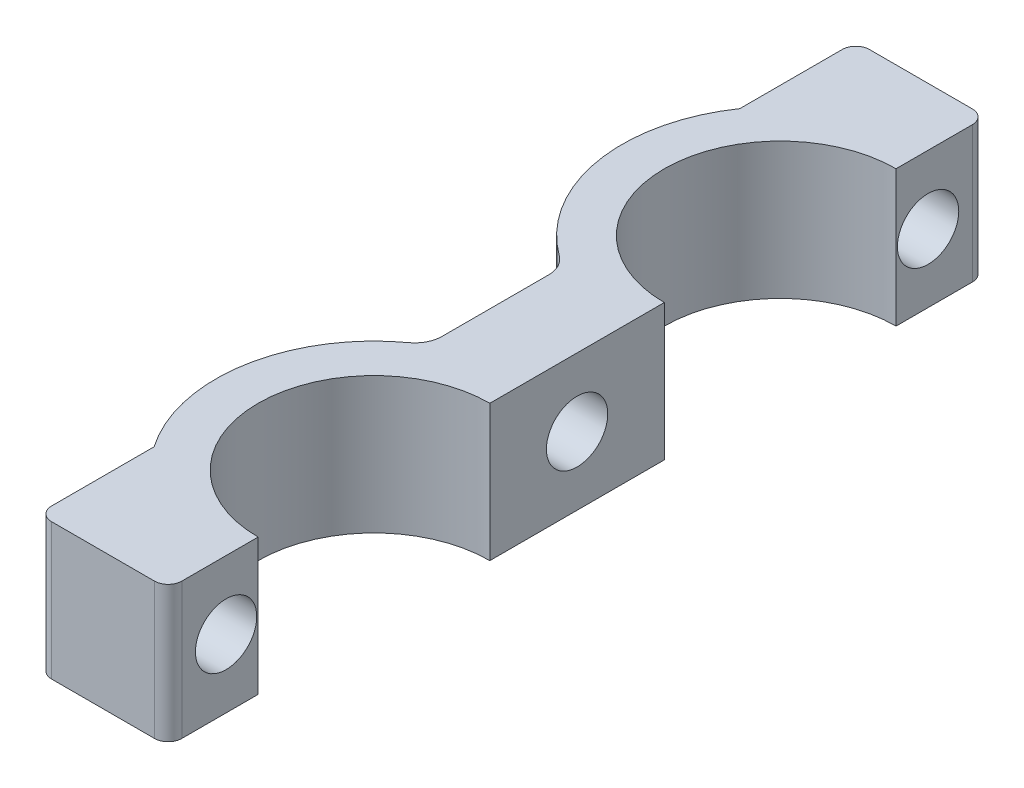
SolidWorks part; units mm, degrees
material "3.1355 (EN-AW 2024)"
ref_plane "Front" through (0, 0, 0) normal (0, 0, 1) x (1, 0, 0)
ref_plane "Top" through (0, 0, 0) normal (0, 1, 0) x (1, 0, 0)
ref_plane "Right" through (0, 0, 0) normal (1, 0, 0) x (0, 0, -1)
sketch "Эскиз1" plane through (0, 0, 0) normal (0, 1, 0) x (1, 0, 0)
  line L0 (0, 0) -> (0, 60) construction
  line L1 (0, 30) -> (-15.0292, 30) construction
  line L2 (0, 0) -> (0, 8)
  line L3 (0, 60) -> (0, 52)
  line L4 (0, 37.8) -> (0, 22.2)
  line L5 (-3, 0) -> (-3, 5.4558)
  line L6 (-3, 35.2558) -> (-3, 24.7442)
  line L7 (-3, 60) -> (-3, 54.5442)
  line L8 (-3, 60) -> (0, 60)
  line L9 (-3, 0) -> (0, 0)
  circle A0 centre (0, 15.1) radius 7.1 construction
  circle A1 centre (0, 44.9) radius 7.1 construction
  arc A2 (0, 8) -> (0, 22.2) centre (0, 15.1) cw
  arc A3 (0, 52) -> (0, 37.8) centre (0, 44.9) ccw
  arc A4 (-3, 5.4558) -> (-3, 24.7442) centre (0, 15.1) cw
  arc A5 (-3, 54.5442) -> (-3, 35.2558) centre (0, 44.9) ccw
  point P9 (0, 22.2)
  dimension "D2" = 15.1
  dimension "D3" = 14.2
  dimension "D1" = 60
  dimension "D4" = 3
extrude "Бобышка-Вытянуть1" add sketch "Эскиз1" along normal blind 10
sketch "Эскиз2" plane through (0, 10, 0) normal (0, 1, 0) x (1, 0, 0)
  line L0 (-3, 60) -> (-8.0498, 60)
  line L1 (-8.0498, 60) -> (-8.0498, 51)
  line L2 (-3, 60) -> (-3, 54.5442)
  line L3 (0, 30) -> (-3, 30) construction
  line L4 (0, 22.2) -> (0, 37.8) construction
  line L5 (-3, 35.2558) -> (-3, 24.7442) construction
  line L6 (-3, 0) -> (-3, 5.4558)
  line L7 (-8.0498, 0) -> (-8.0498, 9)
  line L8 (-3, 0) -> (-8.0498, 0)
  arc A0 (-3, 54.5442) -> (-3, 35.2558) centre (0, 44.9) ccw construction
  arc A1 (-3, 54.5442) -> (-8.0498, 51) centre (0, 44.9) ccw
  arc A2 (-3, 5.4558) -> (-8.0498, 9) centre (0, 15.1) cw
  dimension "D1" = 9
sketch "Эскиз3" plane through (0, 0, 0) normal (-1, 0, 0) x (0, 0, 1)
  line L0 (-60, 5) -> (-54.7288, 5) construction
  line L1 (-60, 10) -> (-60, 0) construction
  line L3 (-30, 10) -> (-30, 0) construction
  line L4 (-35.2558, 10) -> (-24.7442, 10) construction
  line L5 (-35.2558, 0) -> (-24.7442, 0) construction
  circle A0 centre (-55.75, 5) radius 2.25
  circle A1 centre (-4.25, 5) radius 2.25
  point P6 (-58, 5)
  point P7 (-53.5, 5)
  dimension "D1" = 4.5
  dimension "D2" = 2
extrude "Бобышка-Вытянуть2" add sketch "Эскиз2" against normal up to surface (10 mm away) up to face at (-3.8667, 0, -30)
sketch "Эскиз9" plane through (0, 0, 0) normal (0, -1, 0) x (1, 0, 0)
  line L1 (-8.0498, -9) -> (-8.0498, 0) construction
  line L2 (-6, -35.2558) -> (-6, -24.7442)
  line L3 (-6, -34.9723) -> (-6, -25.0277)
  line L4 (-8.0498, 0) -> (-8.0498, -9)
  line L6 (-9.5498, -60) -> (-8.0498, -60)
  line L7 (-3, -35.2558) -> (-3, -24.7442) construction
  line L8 (-3, -35.2558) -> (-3, -24.7442)
  line L9 (-8.0498, -9) -> (-8.0498, 0)
  line L10 (-9.5498, -8.5151) -> (-9.5498, 0)
  line L12 (-9.5498, 0) -> (-8.0498, 0)
  line L13 (-9.5498, -60) -> (-9.5498, -51)
  line L14 (-9.5498, -60) -> (-9.5498, -51.4849)
  line L15 (-8.0498, -60) -> (-8.0498, -51)
  line L16 (-9.5498, -9) -> (-9.5498, 0) construction
  arc A2 (-9.2454, -8.0941) -> (-3.4455, -26.1765) centre (0, -15.1) ccw
  arc A3 (-9.5498, -8.5151) -> (-6, -25.0277) centre (0, -15.1) ccw
  arc A4 (-8.0498, -9) -> (-3, -24.7442) centre (0, -15.1) ccw construction
  arc A5 (-3.4455, -33.8235) -> (-9.2454, -51.9059) centre (0, -44.9) ccw
  arc A6 (-6, -34.9723) -> (-9.5498, -51.4849) centre (0, -44.9) ccw
  arc A7 (-3, -35.2558) -> (-8.0498, -51) centre (0, -44.9) ccw construction
  arc A8 (-8.0498, -9) -> (-3, -24.7442) centre (0, -15.1) ccw
  arc A9 (-3, -35.2558) -> (-8.0498, -51) centre (0, -44.9) ccw
  line M7 (-8.0498, 0) -> (-8.0498, -9)
  arc M9 (-8.0498, -9) -> (-3, -24.7442) centre (0, -15.1) ccw
  line M11 (-3, -24.7442) -> (-3, -35.2558)
  arc M13 (-3, -35.2558) -> (-8.0498, -51) centre (0, -44.9) ccw
  line M15 (-8.0498, -51) -> (-8.0498, -60)
  dimension "D1" = 1.5
  dimension "D2" = 1.5
  dimension "D3" = 3
  dimension "D4" = 1.5
  dimension "D5" = 1.5
extrude "Бобышка-Вытянуть4" add sketch "Эскиз9" against normal through all contours L3 A6 L14 L6 L12 L10 A3 M15 M13 M11 M9 M7 region at (-5.3939, 0, -30)
sketch "Эскиз4" plane through (-6, 0, 0) normal (-1, 0, 0) x (0, 0, 1)
  line L0 (-30, 10) -> (-30, 0) construction
  line L3 (-34.9723, 10) -> (-25.0277, 10) construction
  line L4 (-34.9723, 0) -> (-25.0277, 0) construction
  circle A0 centre (-30, 5) radius 2.25
  dimension "D1" = 4.5
extrude "Вырез-Вытянуть4" cut sketch "Эскиз3" along normal through all
extrude "Вырез-Вытянуть2" cut sketch "Эскиз4" against normal through all
fillet "Скругление2" radius 1 2 edges at (0, 5, 0) (0, 5, -60)
sketch "Эскиз5" plane through (0, 0, 0) normal (0, -1, 0) x (1, 0, 0)
  line L0 (0, -8) -> (0, -8.1)
  line L1 (0, -51.9) -> (0, -52)
  line L2 (0, -37.8) -> (0, -37.9)
  line L3 (0, -22.1) -> (0, -22.2)
  arc A0 (0, -8) -> (0, -22.2) centre (0, -15.1) ccw construction
  arc A1 (0, -37.8) -> (0, -52) centre (0, -44.9) ccw construction
  arc A2 (0, -8) -> (0, -22.2) centre (0, -15.1) ccw
  arc A3 (0, -37.8) -> (0, -52) centre (0, -44.9) ccw
  arc A4 (0, -8.1) -> (0, -22.1) centre (0, -15.1) ccw
  arc A5 (0, -37.9) -> (0, -51.9) centre (0, -44.9) ccw
  dimension "D1" = 0.1
extrude "Бобышка-Вытянуть3" add sketch "Эскиз5" against normal through all
sketch "Эскиз7" plane through (0, 10, 0) normal (0, 1, 0) x (1, 0, 0)
  line L0 (0, 51.9) -> (0, 59) construction
  line L1 (0, 22.1) -> (0, 37.9) construction
  line L2 (0, 1) -> (0, 8.1) construction
  line L3 (0, 51.9) -> (0, 53.4)
  line L4 (0, 22.1) -> (0, 23.6)
  line L5 (0, 6.6) -> (0, 8.1)
  line L6 (0, 36.4) -> (0, 37.9)
  arc A8 (0, 53.4) -> (0, 36.4) centre (0, 44.9) ccw
  arc A9 (0, 53.4) -> (0, 36.4) centre (0, 44.9) ccw
  arc A10 (0, 51.9) -> (0, 37.9) centre (0, 44.9) ccw construction
  arc A11 (0, 23.6) -> (0, 6.6) centre (0, 15.1) ccw
  arc A12 (0, 23.6) -> (0, 6.6) centre (0, 15.1) ccw
  arc A13 (0, 22.1) -> (0, 8.1) centre (0, 15.1) ccw construction
  arc A14 (0, 51.9) -> (0, 37.9) centre (0, 44.9) ccw
  arc A15 (0, 22.1) -> (0, 8.1) centre (0, 15.1) ccw
  dimension "D1" = 1.5
  dimension "D2" = 1.5
extrude "Вырез-Вытянуть3" cut sketch "Эскиз7" against normal through all
fillet "Скругление3" radius 1 2 edges at (-9.5498, 5, 0) (-9.5498, 5, -60)
fillet "Скругление4" radius 2 2 edges at (-6, 5, -34.9723) (-6, 5, -25.0277)
equation "\"D2@Эскиз1\"=8+\"D3@Эскиз1\"/2"
